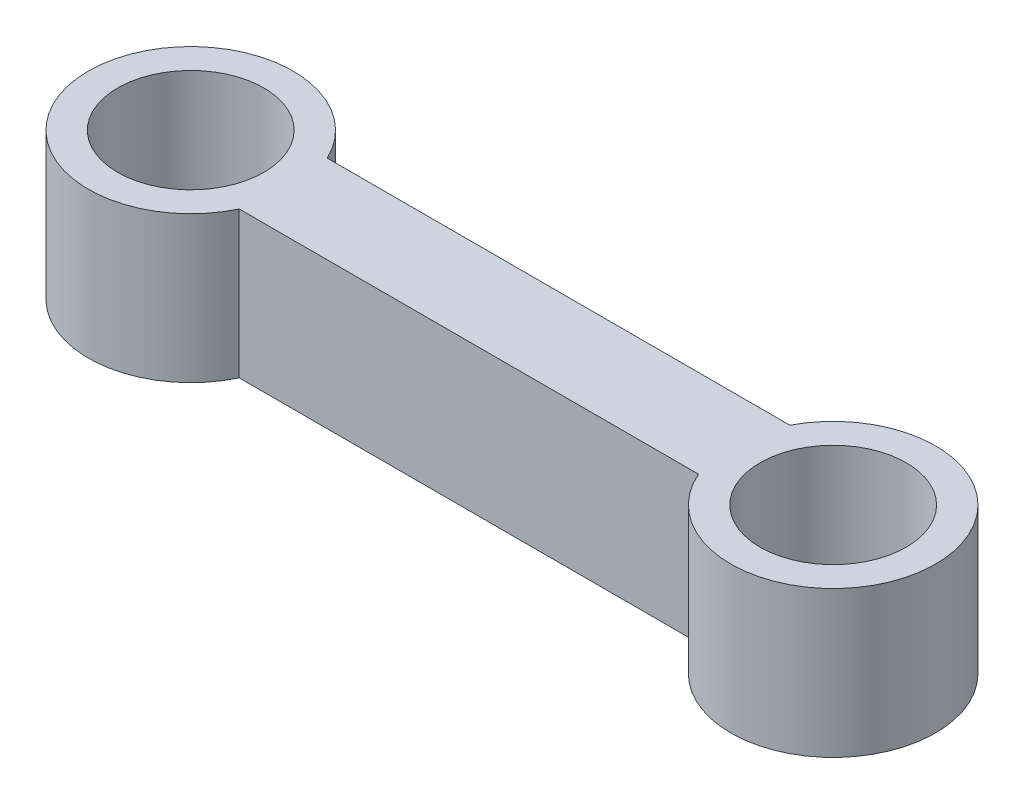
SolidWorks part; units mm, degrees
ref_plane "Plan de face" through (0, 0, 0) normal (0, 0, 1) x (1, 0, 0)
ref_plane "Plan de dessus" through (0, 0, 0) normal (0, 1, 0) x (1, 0, 0)
ref_plane "Plan de droite" through (0, 0, 0) normal (1, 0, 0) x (0, 0, -1)
sketch "Esquisse1" plane through (0, 0, 0) normal (0, 1, 0) x (1, 0, 0)
  line L0 (63.2001, 30.0955) -> (379.4018, 30.0955)
  line L1 (63.2001, -30.0955) -> (377.2097, -30.0955)
  circle A1 centre (0, 0) radius 70
  circle A2 centre (441.4546, -2.2999) radius 70
extrude "Boss.-Extru.2" add sketch "Esquisse1" along normal blind 100 contours A2 L0 A1 L1 | A1 | A2 region at (220.7488, 0, -0.0344) region at (0, 0, 0) region at (441.4546, 0, 2.2999)
sketch "Esquisse2" plane through (0, 100, 0) normal (0, 1, 0) x (1, 0, 0)
  circle A0 centre (0, 0) radius 50
extrude "Enlèv. mat.-Extru.2" cut sketch "Esquisse2" against normal blind 95
sketch "Esquisse4" plane through (0, 100, 0) normal (0, 1, 0) x (1, 0, 0)
  circle A0 centre (441.4546, -2.2999) radius 50
extrude "Enlèv. mat.-Extru.3" cut sketch "Esquisse4" against normal through all contours A0
